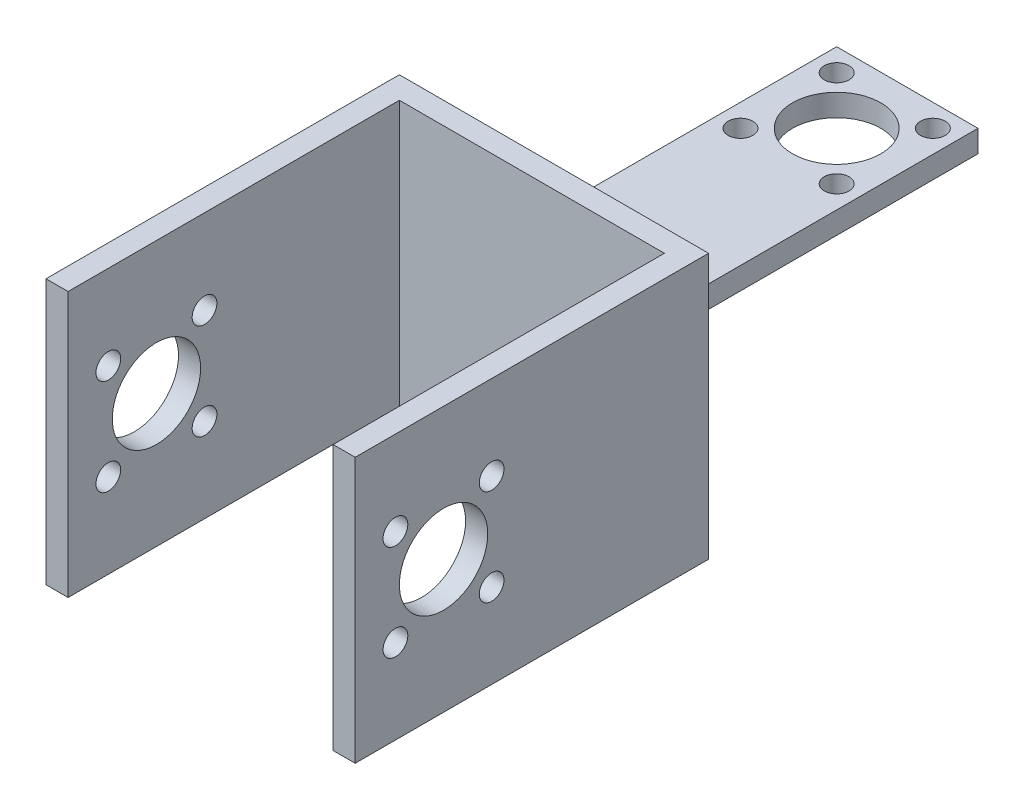
SolidWorks part; units mm, degrees
material "6061-T6 (SS)"
ref_plane "Front Plane" through (0, 0, 0) normal (0, 0, 1) x (1, 0, 0)
ref_plane "Top Plane" through (0, 0, 0) normal (0, 1, 0) x (1, 0, 0)
ref_plane "Right Plane" through (0, 0, 0) normal (1, 0, 0) x (0, 0, -1)
sketch "Sketch1" plane through (0, 0, 0) normal (0, 1, 0) x (1, 0, 0)
  line L0 (0, 0) -> (-20.32, 0)
  line L1 (-20.32, 0) -> (-20.32, -50.8)
  line L2 (0, 0) -> (0, -50.8)
  line L3 (-20.32, -50.8) -> (-32.385, -50.8)
  line L4 (-32.385, -50.8) -> (-32.385, -101.6)
  line L5 (-32.385, -101.6) -> (-29.21, -101.6)
  line L6 (-29.21, -101.6) -> (-29.21, -53.975)
  line L7 (-29.21, -53.975) -> (8.89, -53.975)
  line L8 (8.89, -53.975) -> (8.89, -101.6)
  line L9 (0, -50.8) -> (12.065, -50.8)
  line L10 (8.89, -101.6) -> (12.065, -101.6)
  line L11 (12.065, -50.8) -> (12.065, -101.6)
  line L12 (-10.16, 0) -> (-10.16, -53.975) construction
  dimension "D1" = 20.32
  dimension "D2" = 3.175
  dimension "D3" = 50.8
  dimension "D4" = 38.1
  dimension "D5" = 3.175
  dimension "D10" = 50.8
extrude "Boss-Extrude1" add sketch "Sketch1" along normal mid plane 38.1
sketch "Sketch3" plane through (0, -19.05, 0) normal (0, -1, 0) x (1, 0, 0)
  line L0 (0, 50.8) -> (-20.32, 50.8)
  line L1 (-20.32, 50.8) -> (-20.32, 0)
  line L2 (-20.32, 0) -> (0, 0)
  line L3 (0, 0) -> (0, 50.8)
extrude "Cut-Extrude1" cut sketch "Sketch3" against normal blind 19.05
sketch "Sketch4" plane through (0, 19.05, 0) normal (0, 1, 0) x (1, 0, 0)
  line L0 (-20.32, -50.8) -> (0, -50.8)
  line L1 (0, -50.8) -> (0, 0)
  line L2 (0, 0) -> (-20.32, 0)
  line L3 (-20.32, 0) -> (-20.32, -50.8)
extrude "Cut-Extrude2" cut sketch "Sketch4" against normal blind 15.875
sketch "Sketch6" plane through (0, 3.175, 0) normal (0, 1, 0) x (1, 0, 0)
  line L0 (-10.16, 0) -> (-10.16, -20.32) construction
  line L1 (0, 0) -> (-20.32, 0) construction
  line L2 (-10.16, -10.16) -> (-17.0748, -17.0748) construction
  line L3 (-10.16, -10.16) -> (-17.0748, -3.2452) construction
  line L4 (-10.16, -10.16) -> (-3.2452, -3.2452) construction
  line L5 (-10.16, -10.16) -> (-3.2452, -17.0748) construction
  circle A0 centre (-10.16, -10.16) radius 6.35
  circle A1 centre (-17.0748, -17.0748) radius 1.778
  circle A2 centre (-17.0748, -3.2452) radius 1.778
  circle A3 centre (-3.2452, -3.2452) radius 1.778
  circle A4 centre (-3.2452, -17.0748) radius 1.778
extrude "Cut-Extrude3" cut sketch "Sketch6" against normal up to next
sketch "Sketch9" plane through (12.065, 0, 0) normal (1, 0, 0) x (0, 0, -1)
  line L0 (-101.6, 0) -> (-76.2, 0) construction
  line L1 (-101.6, 19.05) -> (-101.6, -19.05) construction
  line L2 (-88.9, 0) -> (-95.8148, 6.9148) construction
  line L3 (-88.9, 0) -> (-95.8148, -6.9148) construction
  line L4 (-88.9, 0) -> (-81.9852, -6.9148) construction
  line L5 (-88.9, 0) -> (-81.9852, 6.9148) construction
  line L6 (-81.9852, -6.9148) -> (-95.8148, -6.9148) construction
  circle A0 centre (-88.9, 0) radius 6.35
  circle A1 centre (-95.8148, 6.9148) radius 1.778
  circle A2 centre (-81.9852, 6.9148) radius 1.778
  circle A3 centre (-81.9852, -6.9148) radius 1.778
  circle A4 centre (-95.8148, -6.9148) radius 1.778
  dimension "D1" = 19.558
  dimension "D3" = 12.7
  dimension "D4" = 3.556
  dimension "D2" = 12.7
extrude "Cut-Extrude6" cut sketch "Sketch9" against normal up to surface (44.45 mm away) up to face at (-32.385, 0, 76.2)
